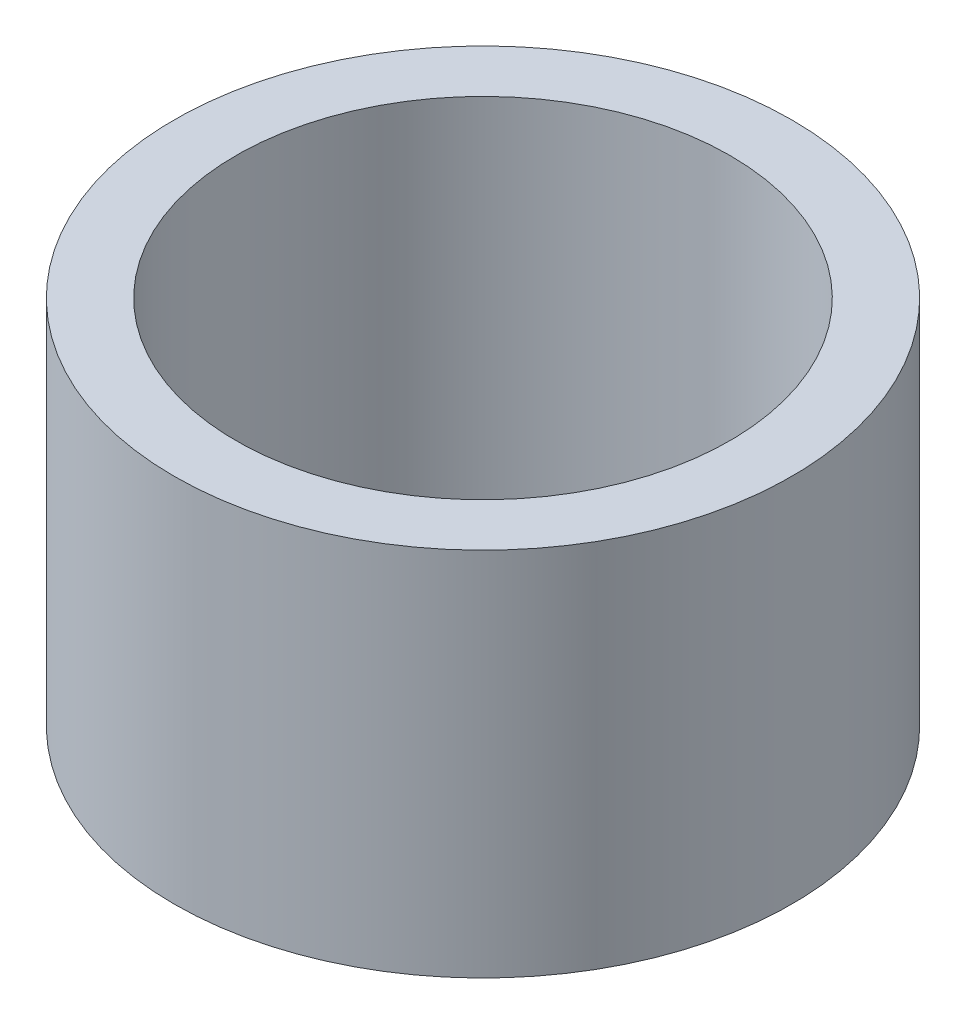
SolidWorks part; units mm, degrees
material "AISI 316 Annealed Stainless Steel Bar (SS)"
ref_plane "Front Plane" through (0, 0, 0) normal (0, 0, 1) x (1, 0, 0)
ref_plane "Top Plane" through (0, 0, 0) normal (0, 1, 0) x (1, 0, 0)
ref_plane "Right Plane" through (0, 0, 0) normal (1, 0, 0) x (0, 0, -1)
sketch "Sketch1" plane through (0, 0, 0) normal (0, 1, 0) x (1, 0, 0)
  circle A0 centre (0, 0) radius 50.8
  circle A1 centre (0, 0) radius 63.5
  dimension "D1" = 127
  dimension "D2" = 12.7
extrude "Boss-Extrude1" add sketch "Sketch1" along normal blind 76.2
